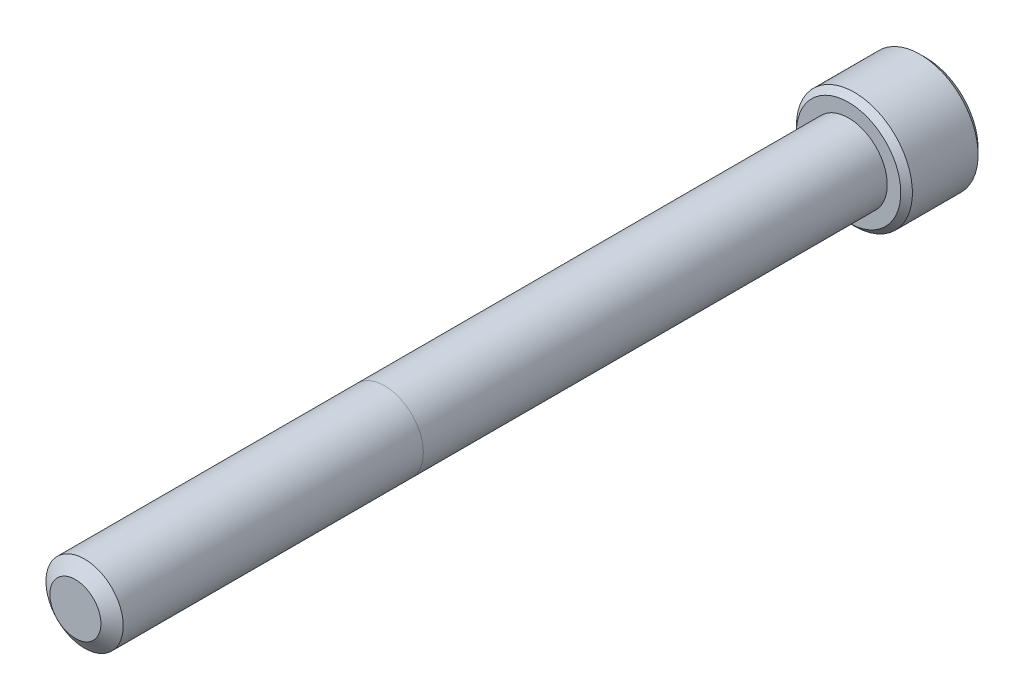
SolidWorks part; units mm, degrees
ref_plane "Front Plane" through (0, 0, 0) normal (0, 0, 1) x (1, 0, 0)
ref_plane "Top Plane" through (0, 0, 0) normal (0, 1, 0) x (1, 0, 0)
ref_plane "Right Plane" through (0, 0, 0) normal (1, 0, 0) x (0, 0, -1)
sketch "Sketch1" plane through (0, 0, 0) normal (0, 0, 1) x (1, 0, 0)
  circle A0 centre (0, 0) radius 3.175
  dimension "OD" = 6.35
extrude "Extrude1" add sketch "Sketch1" against normal blind 63.5
sketch "Sketch2" plane through (0, 0, 0) normal (0, 0, 1) x (1, 0, 0)
  circle A0 centre (0, 0) radius 3.175 construction
  circle A1 centre (0, 0) radius 3.175
curve "Helix/Spiral1" [suppressed] pitch 1.27 height 64.77 turns 51 parameters "pitch"=1.27
sketch "Sketch3" plane through (0, 0, 0) normal (1, 0, 0) x (0, 0, -1)
  line L0 (-1.1113, 3.175) -> (-0.635, 2.3501)
  line L1 (-0.635, 2.3501) -> (-0.4763, 2.3501)
  line L2 (-0.4763, 2.3501) -> (0, 3.175)
  line L3 (-1.1113, 3.175) -> (0, 3.175)
  line L4 (-0.5556, 3.175) -> (-0.5556, 2.3501) construction
  line L5 (-0.8731, 2.7626) -> (-0.2381, 2.7626) construction
  line L6 (0, 3.175) -> (0, -3.175) construction
  dimension "D1" = 0.1588
  dimension "D2" = 0.635
  dimension "D3" = 60
sweep "Cut-Sweep1" [suppressed] cut profiles "Sketch3" path "Helix/Spiral1"
sketch "Sketch4" plane through (0, 0, 0) normal (1, 0, 0) x (0, 0, -1)
  line L0 (0.7554, 3.175) -> (0, 2.0961)
  line L1 (0, 2.0961) -> (0, 3.175)
  line L2 (0.7554, 3.175) -> (0, 3.175)
  line L3 (-1.1113, 3.175) -> (0, 3.175) construction
  line L4 (0, 0) -> (7.0209, 0) construction
  dimension "D1" = 55
  dimension "D2" = 0.254
revolve "Cut-Revolve1" cut sketch "Sketch4" angle 360 about L4
sketch "Sketch5" [suppressed] plane through (0, 0, 0) normal (1, 0, 0) x (0, 0, -1)
  line L0 (63.5, -2.3728) -> (63.5, 2.2654) construction
  line L1 (63.5, 3.302) -> (25.5202, 3.302)
  line L2 (63.5, 3.302) -> (63.5, 0)
  line L3 (63.5, 0) -> (25.4, 0)
  line L4 (25.4, 2.9718) -> (25.4, 0)
  line L5 (25.5202, 3.302) -> (25.4, 2.9718)
  line L6 (0, 0) -> (9.9695, 0) construction
  point P3 (25.4, 3.302)
  point P10 (25.4, 3.302)
  dimension "D1" = 0.3302
  dimension "Thread min" = 25.4
  dimension "D2" = 0.127
  dimension "D3" = 20
revolve "partially thread" [suppressed] add sketch "Sketch5" angle 360 about L6
sketch "Sketch6" plane through (0, 0, -63.5) normal (0, 0, -1) x (-1, 0, 0)
  circle A0 centre (0, 0) radius 4.7625
  dimension "head dia" = 9.525
extrude "Extrude2" add sketch "Sketch6" along normal blind 6.35
sketch "Sketch7" plane through (0, 0, -69.85) normal (0, 0, -1) x (-1, 0, 0)
  line L1 (0, 2.7496) -> (-2.3812, 1.3748)
  line L2 (-2.3812, 1.3748) -> (-2.3813, -1.3748)
  line L3 (-2.3813, -1.3748) -> (0, -2.7496)
  line L4 (0, -2.7496) -> (2.3812, -1.3748)
  line L5 (2.3812, -1.3748) -> (2.3812, 1.3748)
  line L6 (2.3812, 1.3748) -> (0, 2.7496)
  circle A0 centre (0, 0) radius 2.3813 construction
  dimension "hex dia" = 4.7625
extrude "Cut-Extrude1" cut sketch "Sketch7" against normal blind 3.5719
sketch "Sketch8" plane through (0, 0, -69.85) normal (0, 0, -1) x (-1, 0, 0)
  circle A0 centre (0, 0) radius 2.7496
extrude "Cut-Extrude2" cut sketch "Sketch8" against normal through all draft 45
chamfer "Chamfer1" distance 0.4763 angle 45 2 edges at (-4.7625, 0, -69.85) (-4.7625, 0, -63.5)
sketch "Sketch9" plane through (0, 0, 0) normal (1, 0, 0) x (0, 0, -1)
  line L0 (0, 3.175) -> (0, -3.175) construction
  line L1 (6.985, 3.175) -> (6.985, -3.175) construction
  dimension "D1" = 6.985
sketch "Sketch10" plane through (0, 0, 0) normal (0, 1, 0) x (1, 0, 0)
  line L0 (-3.175, 25.4) -> (3.175, 25.4)
  line L1 (-3.175, 63.5) -> (-3.175, 0.7554) construction
  line L2 (3.175, 0.7554) -> (3.175, 63.5) construction
  line L3 (-2.0961, 0) -> (2.0961, 0) construction
  dimension "D1" = 25.4
split line "Split Line1"
equation "\"D3@Helix/Spiral1\" = \"screw length@Extrude1\"+\"pitch@Helix/Spiral1\""
equation "\"D1@Sketch3\" = \"pitch@Helix/Spiral1\"*.125"
equation "\"D2@Sketch3\" = \"pitch@Helix/Spiral1\"*.5"
equation "\"D1@Cut-Extrude1\" = \"hex dia@Sketch7\"*.75"
equation "\"D1@Chamfer1\" = \"head dia@Sketch6\"*.05"
equation "\"D1@Sketch9\" = \"pitch@Helix/Spiral1\"*5.5"
